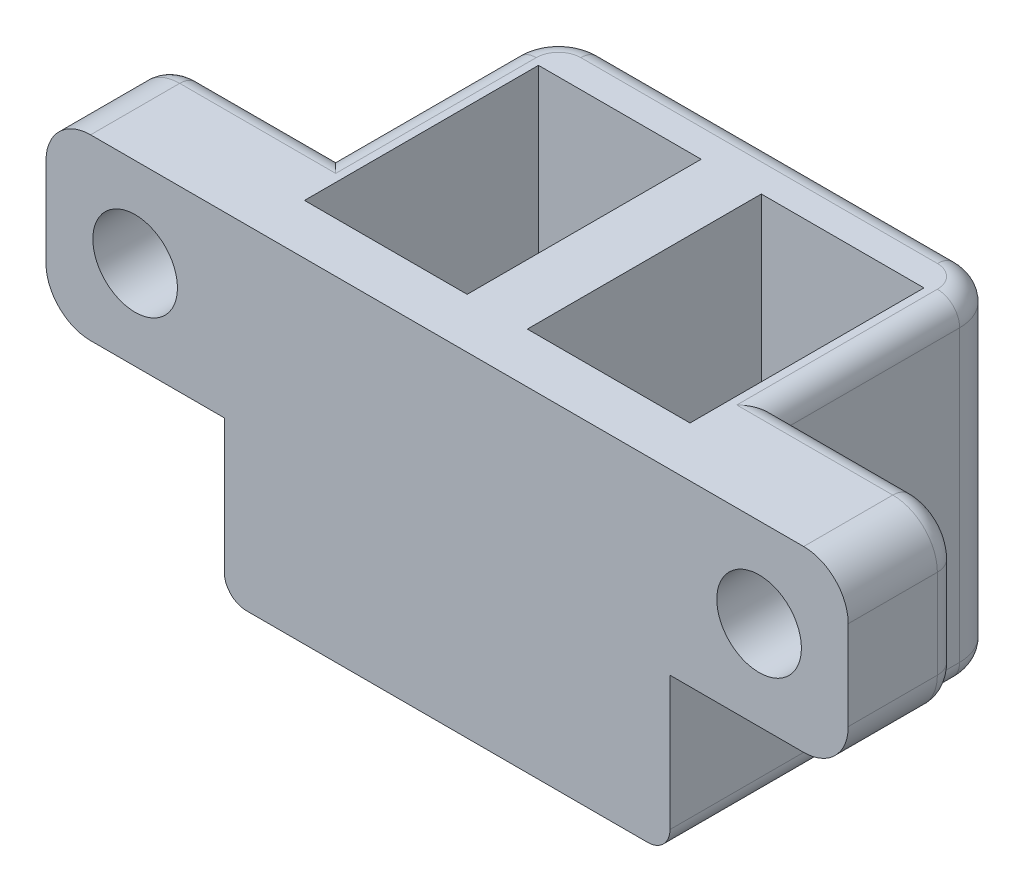
SolidWorks part; units mm, degrees
material "ABS"
ref_plane "Front Plane" through (0, 0, 0) normal (0, 0, 1) x (1, 0, 0)
ref_plane "Top Plane" through (0, 0, 0) normal (0, 1, 0) x (1, 0, 0)
ref_plane "Right Plane" through (0, 0, 0) normal (1, 0, 0) x (0, 0, -1)
sketch "Sketch1" plane through (0, 0, 0) normal (0, 1, 0) x (1, 0, 0)
  line L0 (0, -55) -> (0, 55) construction
  line L1 (-10, 7.5) -> (10, 7.5)
  line L2 (-10, 7.5) -> (-10, -7.5)
  line L3 (-10, -7.5) -> (10, -7.5)
  line L4 (10, 7.5) -> (10, -7.5)
  line L5 (-10, 7.5) -> (10, -7.5) construction
  line L6 (-10, -7.5) -> (10, 7.5) construction
  line L7 (-8.65, 5.25) -> (-1.35, 5.25)
  line L8 (-8.65, 5.25) -> (-8.65, -5.25)
  line L9 (-8.65, -5.25) -> (-1.35, -5.25)
  line L10 (-1.35, 5.25) -> (-1.35, -5.25)
  line L15 (8.65, -5.25) -> (1.35, -5.25)
  line L16 (1.35, 5.25) -> (1.35, -5.25)
  line L17 (8.65, 5.25) -> (1.35, 5.25)
  line L18 (8.65, 5.25) -> (8.65, -5.25)
  line L27 (8.15, -5.25) -> (1.85, -5.25)
  line L28 (-8.15, 5.25) -> (-1.85, 5.25)
  line L29 (-8.15, 5.25) -> (-8.15, -5.25)
  line L30 (-8.15, -5.25) -> (-1.85, -5.25)
  line L31 (-1.85, 5.25) -> (-1.85, -5.25)
  line L32 (-8.15, 5.25) -> (-1.85, -5.25) construction
  line L33 (-8.15, -5.25) -> (-1.85, 5.25) construction
  line L34 (1.85, 5.25) -> (1.85, -5.25)
  line L35 (8.15, 5.25) -> (1.85, 5.25)
  line L36 (8.15, 5.25) -> (8.15, -5.25)
  point P0 (0, 0)
  point P14 (-1.35, 0)
  point P16 (-5, -5.25)
  point P18 (-5, 0)
  point P24 (-5, 5.25)
  dimension "D1" = 20
  dimension "D2" = 15
  dimension "D3" = 10.5
  dimension "D4" = 7.3
  dimension "D5" = 5
  dimension "D6" = 6.3
  dimension "D7" = 10.5
extrude "Boss-Extrude1" add sketch "Sketch1" along normal blind 15 contours L4 L1 L2 L3 L7 L10 L9 L8 L17 L18 L15 L16 region at (0, 0, 0)
extrude "Boss-Extrude2" add sketch "Sketch1<3>" along normal blind 6.5 contours L29 L7 L8 L9 | L7 L31 L9 L10 | L17 L36 L15 L18 | L34 L17 L16 L15 region at (-8.4, 0, 0) region at (-1.6, 0, 0) region at (8.4, 0, 0) region at (1.6, 0, 0)
sketch "Sketch1<3>" plane through (0, 0, 0) normal (0, 1, 0) x (1, 0, 0) same geometry as "Sketch1"
sketch "Sketch2" plane through (0, 0, 7.5) normal (0, 0, 1) x (1, 0, 0)
  line L0 (-10, 7) -> (-16, 7)
  line L3 (-18, 9) -> (-18, 13)
  line L4 (-10, 15) -> (-10, 0) construction
  line L5 (-16, 15) -> (-10, 15)
  line L6 (-10, 15) -> (-10, 7)
  line L7 (0, -55) -> (0, 55) construction
  line L8 (16, 15) -> (10, 15)
  line L9 (18, 9) -> (18, 13)
  line L10 (10, 7) -> (16, 7)
  line L11 (10, 15) -> (10, 7)
  line L12 (-10, 15) -> (10, 15) construction
  arc A2 (-16, 7) -> (-18, 9) centre (-16, 9) cw
  arc A3 (-18, 13) -> (-16, 15) centre (-16, 13) cw
  arc A4 (18, 13) -> (16, 15) centre (16, 13) ccw
  arc A5 (16, 7) -> (18, 9) centre (16, 9) ccw
  point P6 (-18, 7)
  point P13 (-18, 15)
  line M7 (10, 0) -> (10, 15)
  dimension "D4" = 2
  dimension "D1" = 8
  dimension "D3" = 8
extrude "Boss-Extrude3" add sketch "Sketch2" against normal blind 5 contours L10 A5 L9 A4 L8 M7 | L3 A3 L5 L6 L0 A2 region at (13.9021, 11, 7.5)
hole_wizard "#6 Clearance Hole1" positions "Sketch3" profile "Sketch4" hole size "#6" standard "ANSI Inch" end condition through all
sketch "Sketch3" plane through (0, 0, 7.5) normal (0, 0, 1) x (1, 0, 0)
  line L1 (-18, 9) -> (-18, 13) construction
  line L2 (18, 9) -> (18, 13) construction
  point P0 (-14, 11)
  point P2 (14, 11)
  point P9 (-18, 11)
  point P13 (18, 11)
  dimension "D1" = 4
  dimension "D2" = 4
sketch "Sketch4" plane through (-14, 11, 7.5) normal (1, 0, 0) x (0, -1, 0)
  line L0 (0, 0) -> (0, 15)
  line L1 (0, 15) -> (1.8986, 15)
  line L2 (1.8986, 15) -> (1.8986, 0)
  line L5 (1.8986, 0) -> (0, 0)
  line L11 (0, -6.35) -> (0, 107.95) construction
  dimension "Thru Hole Dia." = 3.7973
  dimension "Thru Hole Depth" = 15
sketch "Sketch5" plane through (0, 0, 0) normal (0, -1, 0) x (1, 0, 0)
  line L1 (-8.15, 5.25) -> (-1.85, 5.25)
  line L2 (-8.15, 5.25) -> (-8.15, -5.25)
  line L3 (-8.15, -5.25) -> (-1.85, -5.25)
  line L4 (-1.85, 5.25) -> (-1.85, -5.25)
  line L5 (-8.15, 5.25) -> (-1.85, -5.25) construction
  line L6 (-8.15, -5.25) -> (-1.85, 5.25) construction
  line L7 (-8.15, 5.25) -> (-1.85, 5.25) construction
  line L8 (0, -8.25) -> (0, 8.25) construction
  line L9 (-7.15, 4.25) -> (-2.85, 4.25)
  line L10 (-7.15, 4.25) -> (-7.15, -4.25)
  line L11 (-7.15, -4.25) -> (-2.85, -4.25)
  line L12 (-2.85, 4.25) -> (-2.85, -4.25)
  line L13 (-7.15, 4.25) -> (-2.85, -4.25) construction
  line L14 (-7.15, -4.25) -> (-2.85, 4.25) construction
  line L15 (8.15, -5.25) -> (1.85, -5.25)
  line L16 (1.85, 5.25) -> (1.85, -5.25)
  line L17 (8.15, 5.25) -> (1.85, 5.25)
  line L18 (8.15, 5.25) -> (8.15, -5.25)
  line L19 (7.15, -4.25) -> (2.85, -4.25)
  line L20 (2.85, 4.25) -> (2.85, -4.25)
  line L21 (7.15, 4.25) -> (2.85, 4.25)
  line L22 (7.15, 4.25) -> (7.15, -4.25)
  line L23 (-1.85, -5.25) -> (-1.85, 5.25) construction
  point P0 (-5, 0)
  point P13 (-5, 0)
  dimension "D1" = 1
  dimension "D2" = 1
  dimension "D3" = 3.15
extrude "Boss-Extrude4" add sketch "Sketch5" against normal blind 1.5
fillet "Fillet1" radius 2 2 edges at (10, 7.5, -7.5) (-10, 7.5, -7.5)
fillet "Fillet2" radius 1 8 edges at (7.15, 1.5, 0) (5, 1.5, 4.25) (5, 1.5, -4.25) (2.85, 1.5, 0) (-7.15, 1.5, 0) (-5, 1.5, 4.25) (-5, 1.5, -4.25) (-2.85, 1.5, 0) profile chamfer
fillet "Fillet3" radius 1 20 edges at (-10, 15, -1.5) (-9.4142, 15, -6.9142) (0, 15, -7.5) (9.4142, 15, -6.9142) (10, 15, -1.5) (-13, 7, 2.5) (-17.4142, 7.5858, 2.5) (-18, 11, 2.5) (-17.4142, 14.4142, 2.5) (13, 7, 2.5) (17.4142, 7.5858, 2.5) (18, 11, 2.5) (17.4142, 14.4142, 2.5) (-13, 15, 2.5) (13, 15, 2.5) (-10, 0, 1) (-9.4142, 0, -6.9142) (0, 0, -7.5) (9.4142, 0, -6.9142) (10, 0, 1)
equation "\"D5@Sketch1\"=\"D1@Sketch1\"/4"
equation "\"D1@Boss-Extrude2\"=15-8.5"
equation "\"D6@Sketch1\"=\"D4@Sketch1\"-1"
equation "\"D7@Sketch1\"=\"D3@Sketch1\""
equation "\"D3@Sketch5\"=6.3/2"
